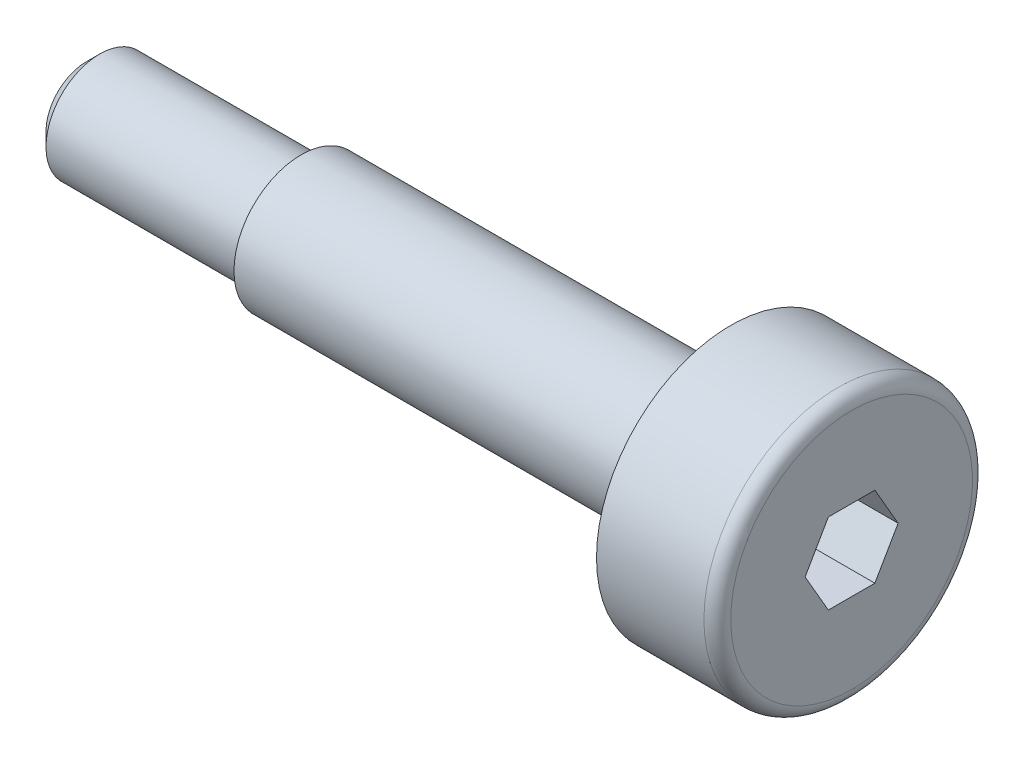
SolidWorks part; units mm, degrees
material "AISI 1020"
ref_plane "XY (Front)" through (0, 0, 0) normal (0, 0, 1) x (1, 0, 0)
ref_plane "XZ (Top)" through (0, 0, 0) normal (0, 1, 0) x (1, 0, 0)
ref_plane "YZ (Right)" through (0, 0, 0) normal (1, 0, 0) x (0, 0, -1)
ref_axis "X" through (-25.2, 0, 0) along (1, 0, 0)
ref_axis "Y" through (0, 5.5, 0) along (0, -1, 0)
ref_axis "Z" through (0, 0, -5.5) along (0, 0, 1)
sketch "Sketch1" plane through (0, 0, 0) normal (0, 0, 1) x (1, 0, 0)
  line L0 (0, 0) -> (0, 4.5)
  line L1 (-0.5, 5) -> (-4.5, 5)
  line L2 (-4.5, 5) -> (-4.5, 2.5)
  line L3 (-4.5, 2.5) -> (-20.5, 2.5)
  line L4 (-20.5, 2.5) -> (-20.5, 2)
  line L5 (-20.5, 2) -> (-28.5, 2)
  line L6 (-28.5, 2) -> (-28.5, 0)
  line L7 (-28.5, 0) -> (0, 0)
  line L8 (0, 0) -> (5.7531, 0) construction
  arc A0 (0, 4.5) -> (-0.5, 5) centre (-0.5, 4.5) ccw
  dimension "R" = 0.5
  dimension "d3" = 10
  dimension "d1" = 5
  dimension "M" = 4
  dimension "l3" = 4.5
  dimension "l1" = 16
  dimension "l2" = 8
revolve "Revolve1" add sketch "Sketch1" angle 360 about L8
chamfer "Chamfer1" distance 0.5 angle 45 1 edges at (-28.5, 0, 2)
sketch "Sketch2" plane through (0, 0, 0) normal (1, 0, 0) x (0, 0, -1)
  line L1 (1.7321, 0) -> (0.866, 1.5)
  line L2 (0.866, 1.5) -> (-0.866, 1.5)
  line L3 (-0.866, 1.5) -> (-1.7321, 0)
  line L4 (-1.7321, 0) -> (-0.866, -1.5)
  line L5 (-0.866, -1.5) -> (0.866, -1.5)
  line L6 (0.866, -1.5) -> (1.7321, 0)
  circle A0 centre (0, 0) radius 1.5 construction
  dimension "AF" = 3
extrude "Cut-Extrude1" cut sketch "Sketch2" against normal blind 2.4
